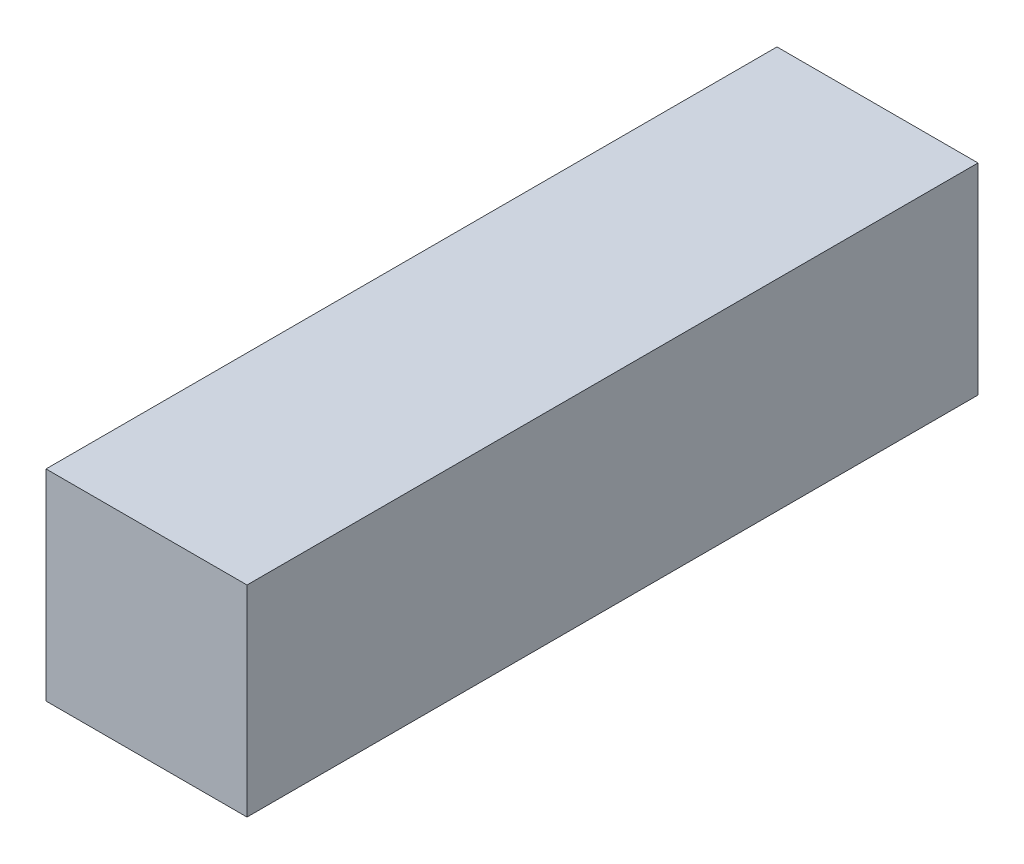
SolidWorks part; units mm, degrees
material "PLA"
ref_plane "Front Plane" through (0, 0, 0) normal (1, 0, 0) x (0, 1, 0)
ref_plane "Top Plane" through (0, 0, 0) normal (0, 0, 1) x (0, 1, 0)
ref_plane "Right Plane" through (0, 0, 0) normal (0, 1, 0) x (-1, 0, 0)
sketch "Sketch1" plane through (0, 0, 0) normal (0, 0, 1) x (0, 1, 0)
  line L1 (-13.75, -13.75) -> (13.75, -13.75)
  line L2 (-13.75, -13.75) -> (-13.75, 13.75)
  line L3 (-13.75, 13.75) -> (13.75, 13.75)
  line L4 (13.75, -13.75) -> (13.75, 13.75)
  line L5 (-13.75, -13.75) -> (13.75, 13.75) construction
  line L6 (-13.75, 13.75) -> (13.75, -13.75) construction
  point P0 (0, 0)
  dimension "D2" = 27.5
extrude "Boss-Extrude1" add sketch "Sketch1" along normal blind 100
equation "\"ball_diameter\"= 3cm"
equation "\"wall_thickness\" = 0.25cm"
equation "\"track_length\" = 25cm"
equation "\"axle\" = 5mm"
equation "\"pillar_width\" = 2.75cm"
equation "\"D2@Sketch1\"=\"pillar_width\""
